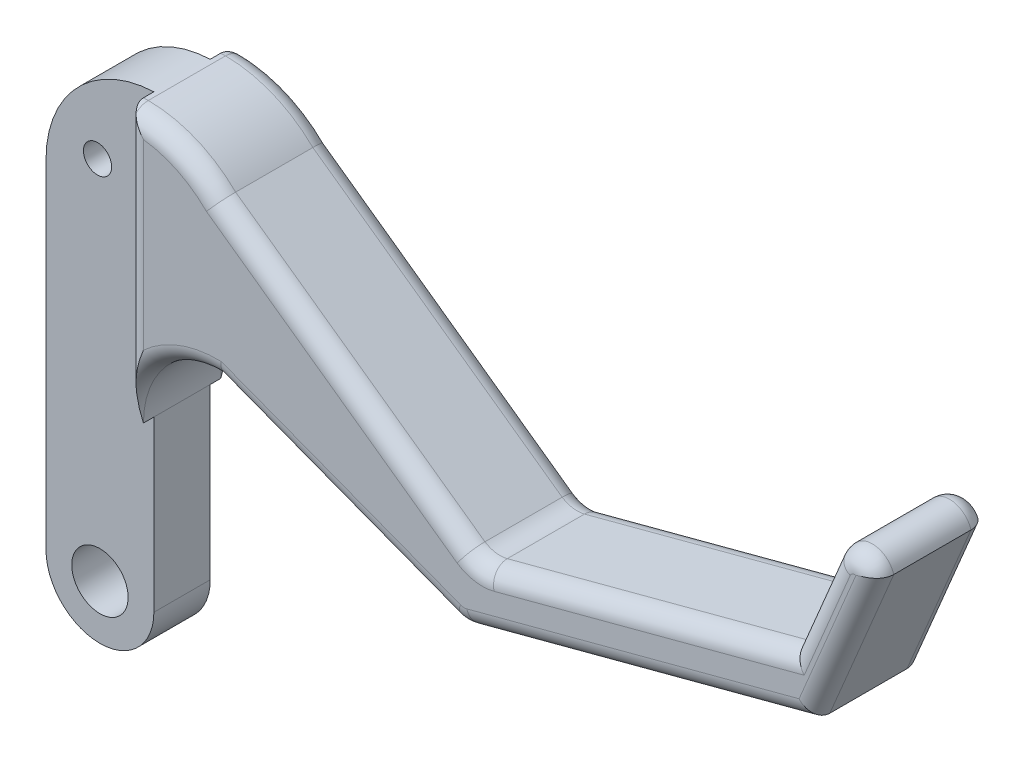
SolidWorks part; units mm, degrees
material "Aleación 1060"
ref_plane "Alzado" through (0, 0, 0) normal (0, 0, 1) x (1, 0, 0)
ref_plane "Planta" through (0, 0, 0) normal (0, 1, 0) x (1, 0, 0)
ref_plane "Vista lateral" through (0, 0, 0) normal (1, 0, 0) x (0, 0, -1)
sketch "Croquis1" plane through (0, 0, 0) normal (0, 0, 1) x (1, 0, 0)
  line L0 (0, 0) -> (0, 38.1)
  line L1 (0, 50.8) -> (88.9, 50.8) construction
  line L2 (12.1546, 0) -> (12.1546, 19.05)
  line L3 (22.5449, 29.4403) -> (49.1627, 19.3059)
  line L4 (51.1077, 19.2046) -> (89.4888, 29.4024)
  line L5 (89.4888, 29.4024) -> (96.6956, 46.545)
  line L6 (87.1397, 35.3486) -> (91.9447, 46.778)
  line L7 (87.1397, 35.3486) -> (53.1505, 26.3177)
  line L9 (22.5449, 46.778) -> (50.6329, 26.7061)
  arc A0 (12.1546, 19.05) -> (22.5449, 29.4403) centre (22.5449, 19.05) cw
  arc A1 (0, 0) -> (12.1546, 0) centre (6.0773, 0) ccw
  arc A2 (0, 38.1) -> (12.7, 50.8) centre (12.7, 38.1) cw
  arc A3 (50.6329, 26.7061) -> (53.1505, 26.3177) centre (52.3352, 29.3862) ccw
  arc A4 (49.1627, 19.3059) -> (51.1077, 19.2046) centre (50.2924, 22.2731) ccw
  arc A5 (12.7, 50.8) -> (22.5449, 46.778) centre (12.7, 36.7399) cw
  arc A6 (91.9447, 46.778) -> (96.6956, 46.545) centre (94.2778, 45.7972) cw
  dimension "D6" = 6.35
  dimension "D7" = 6.35
  dimension "D1" = 50.8
  dimension "D2" = 88.9
  dimension "D3" = 19.05
  dimension "D4" = 6.35
  dimension "D5" = 38.1
extrude "Saliente-Extruir1" add sketch "Croquis1" along normal mid plane 12.7
sketch "Croquis2" plane through (0, 0, 6.35) normal (0, 0, 1) x (1, 0, 0)
  circle A0 centre (6.0773, 0) radius 3.175
  dimension "D1" = 6.35
extrude "Cortar-Extruir1" cut sketch "Croquis2" against normal through all
sketch "Croquis3" plane through (0, 0, 6.35) normal (0, 0, 1) x (1, 0, 0)
  line L0 (12.1546, 0) -> (12.1546, 57.7172)
  line L1 (12.1546, 57.7172) -> (-8.9453, 57.7172)
  line L2 (-8.9453, 57.7172) -> (-8.9453, -10.8837)
  line L3 (-8.9453, -10.8837) -> (12.1546, -10.8837)
  line L4 (12.1546, -10.8837) -> (12.1546, 0)
extrude "Cortar-Extruir2" cut sketch "Croquis3" against normal blind 3.175
sketch "Croquis4" plane through (0, 0, -6.35) normal (0, 0, -1) x (-1, 0, 0)
  line L0 (-12.1546, 0) -> (-12.1546, 59.6772)
  line L1 (-12.1546, 59.6772) -> (8.9453, 59.6772)
  line L2 (8.9453, 59.6772) -> (8.9453, -9.9791)
  line L3 (8.9453, -9.9791) -> (-12.1546, -9.9791)
  line L4 (-12.1546, -9.9791) -> (-12.1546, 0)
extrude "Cortar-Extruir3" cut sketch "Croquis4" against normal blind 3.175
fillet "Redondeo6" radius 2 24 edges at (18.0174, 49.7557, 6.35) (36.5889, 36.7421, 6.35) (51.851, 26.2483, 6.35) (70.1451, 30.8331, 6.35) (89.5422, 41.0633, 6.35) (94.4018, 48.325, 6.35) (93.0922, 37.9737, 6.35) (70.2983, 24.3035, 6.35) (50.1272, 19.1024, 6.35) (35.8538, 24.3731, 6.35) (15.1979, 26.397, 6.35) (12.1546, 34.9191, 6.35) (35.8538, 24.3731, -6.35) (50.1272, 19.1024, -6.35) (70.2983, 24.3035, -6.35) (93.0922, 37.9737, -6.35) (94.4018, 48.325, -6.35) (89.5422, 41.0633, -6.35) (70.1451, 30.8331, -6.35) (51.851, 26.2483, -6.35) (36.5889, 36.7421, -6.35) (18.0174, 49.7557, -6.35) (12.1546, 34.9191, -6.35) (15.1979, 26.397, -6.35)
sketch "Croquis5" plane through (0, 0, 3.175) normal (0, 0, 1) x (1, 0, 0)
  line L0 (12.1546, 19.05) -> (12.1546, 50.7883) construction
  circle A0 centre (5.8046, 41.075) radius 1.5875
  dimension "D1" = 6.35
  dimension "D2" = 3.175
extrude "Cortar-Extruir4" cut sketch "Croquis5" against normal blind 76.2
